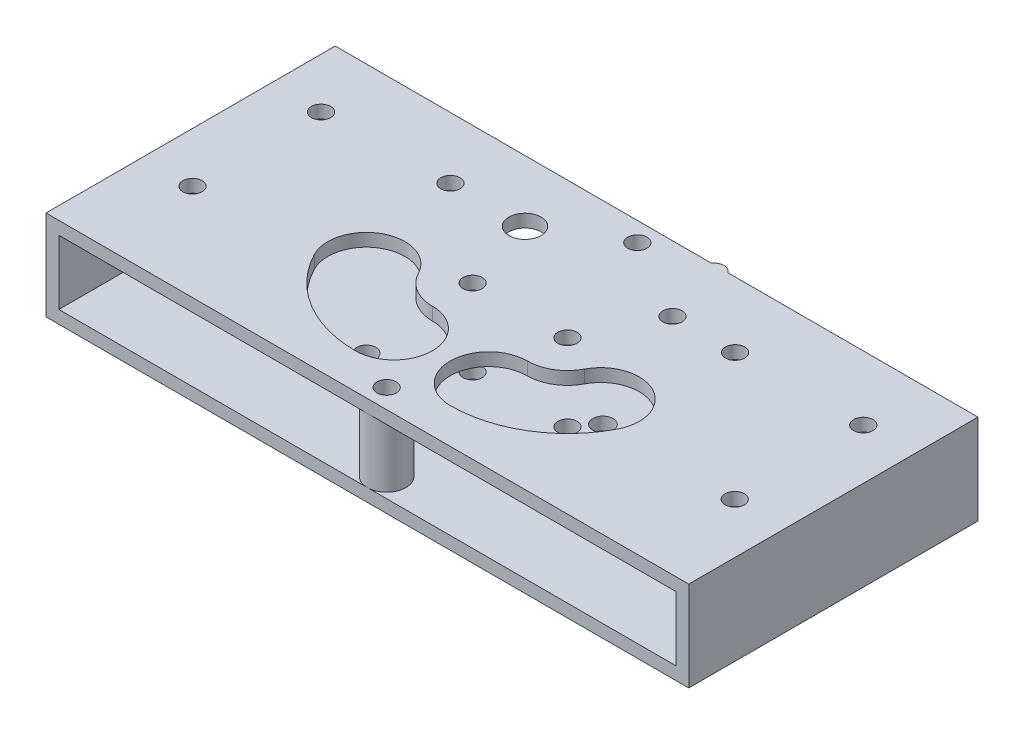
SolidWorks part; units mm, degrees
material "ABS PC"
ref_plane "Front Plane" through (0, 0, 0) normal (0, 0, 1) x (1, 0, 0)
ref_plane "Top Plane" through (0, 0, 0) normal (0, 1, 0) x (1, 0, 0)
ref_plane "Right Plane" through (0, 0, 0) normal (1, 0, 0) x (0, 0, -1)
sketch "Sketch2" plane through (0, 0, 0) normal (0, 1, 0) x (1, 0, 0)
  line L1 (50, -20) -> (-50, -20)
  line L2 (50, -20) -> (50, 20)
  line L3 (50, 20) -> (-50, 20)
  line L4 (-50, -20) -> (-50, 20)
  line L5 (50, -20) -> (-50, 20) construction
  line L6 (50, 20) -> (-50, -20) construction
  point P0 (0, 0)
  dimension "D1" = 40
  dimension "D2" = 100
extrude "Boss-Extrude5" add sketch "Sketch2" along normal blind 14
shell "Shell1" thickness 2 removed face at (0, 7, -20) removed face at (0, 7, 20)
sketch "Sketch3" plane through (0, 14, 0) normal (0, 1, 0) x (1, 0, 0)
  line L0 (0, 8.1159) -> (0, 14.8792) construction
  line L1 (-50, -20) -> (50, -20) construction
  line L3 (37.1507, -20) -> (27.2757, -20) construction
  line L4 (37.1507, -20) -> (37.1507, 20) construction
  line L5 (37.1507, 20) -> (27.2757, 20) construction
  line L6 (27.2757, -20) -> (27.2757, 20) construction
  line L7 (-50, -20) -> (50, -20) construction
  line L8 (50, 20) -> (-50, 20) construction
  line L10 (-37.2143, -20) -> (-27.3343, -20) construction
  line L11 (-37.2143, -20) -> (-37.2143, 20) construction
  line L12 (-37.2143, 20) -> (-27.3343, 20) construction
  line L13 (-27.3343, -20) -> (-27.3343, 20) construction
  circle A0 centre (7.3745, -1.251) radius 1.5
  arc A6 (7.3745, -13.5) -> (18.2286, -6.9279) centre (7.3745, -1.251) ccw construction
  arc A14 (7.3745, -15) -> (19.5578, -7.623) centre (7.3745, -1.251) ccw
  arc A15 (7.3745, -12) -> (16.8994, -6.2327) centre (7.3745, -1.251) ccw
  arc A16 (7.3745, -12) -> (7.3745, -15) centre (7.3745, -13.5) ccw
  arc A17 (19.5578, -7.623) -> (16.8994, -6.2327) centre (18.2286, -6.9279) ccw
  arc A18 (-7.3745, -13.5) -> (-18.2286, -6.9279) centre (-7.3745, -1.251) cw construction
  arc A19 (-7.3745, -15) -> (-19.5578, -7.623) centre (-7.3745, -1.251) cw
  arc A20 (-7.3745, -12) -> (-16.8994, -6.2327) centre (-7.3745, -1.251) cw
  arc A21 (-7.3745, -12) -> (-7.3745, -15) centre (-7.3745, -13.5) cw
  arc A22 (-19.5578, -7.623) -> (-16.8994, -6.2327) centre (-18.2286, -6.9279) cw
  circle A23 centre (-7.3745, -1.251) radius 1.5
  circle A24 centre (7.3745, -1.251) radius 7.375 construction
  arc A25 (7.3745, -13.5) -> (18.2286, -6.9279) centre (7.3745, -1.251) ccw construction
  arc A26 (7.3745, -19.5) -> (23.5453, -9.7086) centre (7.3745, -1.251) ccw
  arc A27 (7.3745, -7.5) -> (12.9119, -4.1471) centre (7.3745, -1.251) ccw
  arc A28 (7.3745, -7.5) -> (7.3745, -19.5) centre (7.3745, -13.5) ccw
  arc A29 (23.5453, -9.7086) -> (12.9119, -4.1471) centre (18.2286, -6.9279) ccw
  circle A30 centre (12.6507, 9.8045) radius 4.875 construction
  circle A31 centre (18.2286, -6.9279) radius 6 construction
  circle A32 centre (12.6507, 9.8045) radius 6 construction
  circle A33 centre (-7.3745, -1.251) radius 7.3745 construction
  circle A34 centre (22.4007, 9.8045) radius 4.875 construction
  circle A35 centre (22.4007, 9.8045) radius 6 construction
  circle A36 centre (22.4007, 9.8045) radius 1.5
  circle A37 centre (12.6507, 9.8045) radius 1.5
  circle A38 centre (-10.9443, 10.4668) radius 4.875 construction
  circle A39 centre (-10.9443, 10.4668) radius 6 construction
  circle A40 centre (-10.9443, 10.4668) radius 2.5
  circle A41 centre (42.1507, 10) radius 5 construction
  circle A42 centre (42.1507, -10) radius 5 construction
  circle A43 centre (-42.2143, 10) radius 5 construction
  circle A44 centre (-42.2143, -10) radius 5 construction
  circle A45 centre (-22.548, 10.4668) radius 4.7863 construction
  arc A46 (-7.3745, -13.5) -> (-18.2286, -6.9279) centre (-7.3745, -1.251) cw construction
  arc A47 (-7.3745, -19.5) -> (-23.5453, -9.7086) centre (-7.3745, -1.251) cw
  arc A48 (-7.3745, -7.5) -> (-12.9119, -4.1471) centre (-7.3745, -1.251) cw
  arc A49 (-7.3745, -7.5) -> (-7.3745, -19.5) centre (-7.3745, -13.5) cw
  arc A50 (-23.5453, -9.7086) -> (-12.9119, -4.1471) centre (-18.2286, -6.9279) cw
  circle A51 centre (-18.2286, -6.9279) radius 6 construction
  circle A52 centre (-42.2143, -10) radius 1.5
  circle A53 centre (-42.2143, 10) radius 1.5
  circle A54 centre (-22.548, 10.4668) radius 1.5
  circle A55 centre (42.1507, 10) radius 1.5
  circle A56 centre (42.1507, -10) radius 1.5
  point P7 (13.7189, -11.7289)
  point P15 (-13.7189, -11.7289)
  point P25 (13.7189, -11.7289)
  point P69 (-13.7189, -11.7289)
  dimension "D1" = 3
  dimension "D2" = 3
  dimension "D5" = 5
  dimension "D7" = 14.75
  dimension "D8" = 12
  dimension "D9" = 9.75
  dimension "D10" = 12
  dimension "D11" = 12
  dimension "D12" = 9.875
  dimension "D13" = 10
  dimension "D14" = 10
  dimension "D16" = 5
  dimension "D3" = 14.749
  dimension "D4" = 12.249
  dimension "D6" = 14.749
  dimension "D15" = 10
  dimension "D17" = 9.88
extrude "Cut-Extrude8" cut sketch "Sketch3<6>" against normal through all contours A40 | A52 | A53 | A54 | A23 | A0 | A37 | A36 | A14 A17 A15 A16 | A19 A22 A20 A21 | A55 | A56 region at (-10.9443, 14, -10.4668)
sketch "Sketch3<6>" plane through (0, 14, 0) normal (0, 1, 0) x (1, 0, 0) same geometry as "Sketch3"
extrude "Cut-Extrude9" cut sketch "Sketch3" against normal blind 12 contours A50 A47 A49 A48 A19 A22 A20 A21 | A26 A29 A27 A28 A17 A14 A16 A15 region at (1.669, 14, 13.5) region at (-16.674, 14, 16.6095)
sketch "Sketch5" plane through (0, 0, 20) normal (0, 0, 1) x (1, 0, 0)
  line L0 (-48, 2) -> (48, 2) construction
  line L1 (50, 0) -> (-50, 0)
  line L2 (50, 0) -> (50, 14)
  line L3 (50, 14) -> (-50, 14)
  line L4 (-50, 0) -> (-50, 14)
  line L5 (-48, 12) -> (48, 12)
  line L6 (-48, 12) -> (-48, 2)
  line L7 (-48, 2) -> (48, 2)
  line L8 (48, 12) -> (48, 2)
  line L9 (48, 12) -> (48, 2) construction
extrude "Boss-Extrude6" add sketch "Sketch5" along normal blind 5
sketch "Sketch6" plane through (0, 14, 0) normal (0, 1, 0) x (1, 0, 0)
  line L0 (50, 20) -> (-50, 20) construction
  line L1 (50, -25) -> (-50, -25) construction
  line L2 (9.8044, 19.0918) -> (9.8044, 1.8418) construction
  line L3 (9.8044, 1.8418) -> (-0.9443, 10.4668) construction
  line L4 (9.8044, 19.0918) -> (-0.9443, 10.4668) construction
  circle A0 centre (0, 17) radius 3
  circle A1 centre (0, -22) radius 3
  circle A2 centre (0, -22) radius 1.5
  circle A3 centre (0, 17) radius 1.5
  circle A4 centre (-10.9443, 10.4668) radius 22.47 construction
  circle A5 centre (9.8044, 19.0918) radius 1.58
  circle A6 centre (9.8044, 1.8418) radius 1.58
  circle A7 centre (-10.9443, 10.4668) radius 10 construction
  circle A8 centre (-0.9443, 10.4668) radius 1.95
  dimension "D1" = 6
  dimension "D2" = 3
  dimension "D3" = 44.94
  dimension "D5" = 3.16
  dimension "D6" = 20
  dimension "D7" = 3.9
  dimension "D4" = 17.25
extrude "Boss-Extrude7" add sketch "Sketch6" against normal through all
extrude "Cut-Extrude11" cut sketch "Sketch6<2>" against normal through all contours A2 | A3
sketch "Sketch6<2>" plane through (0, 14, 0) normal (0, 1, 0) x (1, 0, 0) same geometry as "Sketch6"
extrude "Cut-Extrude12" cut sketch "Sketch6<3>" along direction (0, 1, 0) on the side against the normal through all from surface contours A6 | A5 | A8 starting at face at (-0.9443, 12, -8.5168)
sketch "Sketch6<3>" plane through (0, 14, 0) normal (0, 1, 0) x (1, 0, 0) same geometry as "Sketch6"
